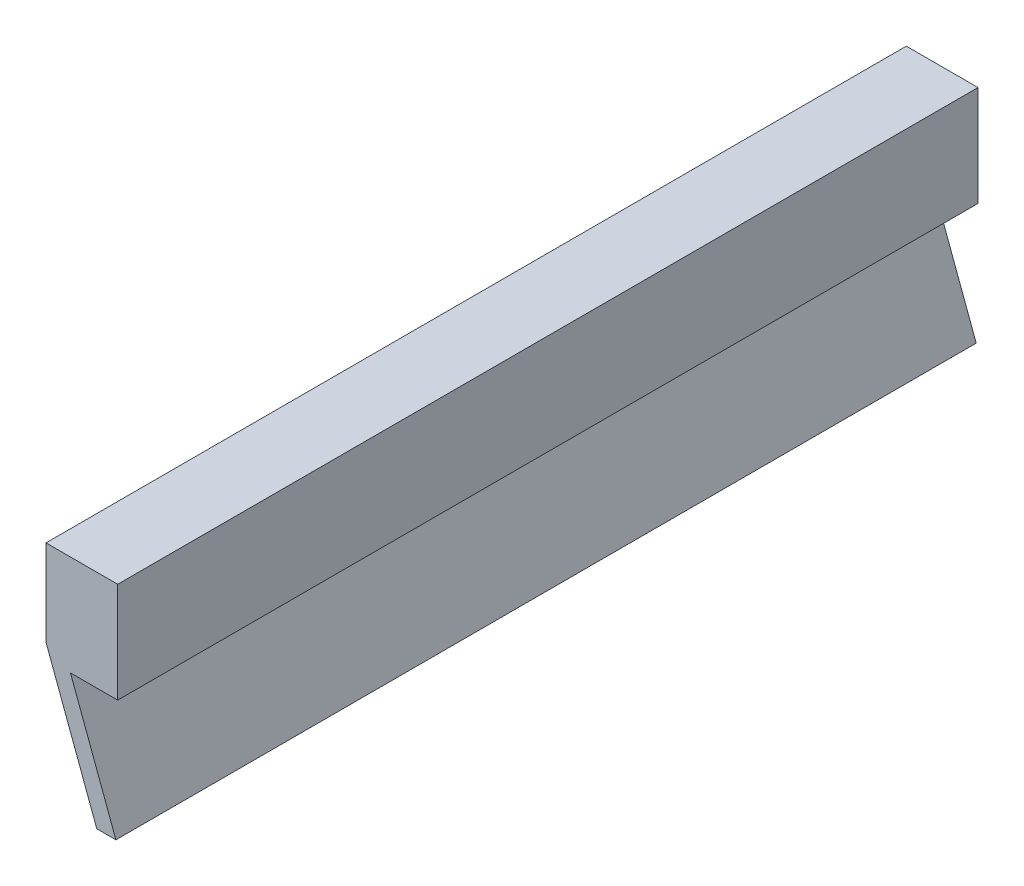
SolidWorks part; units mm, degrees
ref_plane "Alzado" through (0, 0, 0) normal (0, 0, 1) x (1, 0, 0)
ref_plane "Planta" through (0, 0, 0) normal (0, 1, 0) x (1, 0, 0)
ref_plane "Vista lateral" through (0, 0, 0) normal (1, 0, 0) x (0, 0, -1)
sketch "Croquis1" plane through (0, 0, 0) normal (0, 0, 1) x (1, 0, 0)
  line L0 (0, 0) -> (-6.5865, 0)
  line L1 (-6.5865, 0) -> (-0.25, -17)
  line L2 (-0.25, -17) -> (-0.25, -20)
  line L3 (-0.25, -20) -> (-2.918, -20)
  line L4 (-2.918, -20) -> (-2.918, -17)
  line L5 (-2.918, -17) -> (-10, 2)
  line L6 (-10, 2) -> (-10, 14)
  line L7 (-10, 14) -> (0, 14)
  line L8 (0, 14) -> (0, 0)
  line L9 (-0.25, -17) -> (-2.918, -17)
  line L10 (0, 14) -> (0, -24.8871) construction
  dimension "D1" = 2.5
  dimension "D2" = 3
  dimension "D3" = 10
  dimension "D4" = 20
  dimension "D5" = 0.5
  dimension "D6" = 12
  dimension "D7" = 14
extrude "Saliente-Extruir1" add sketch "Croquis1" along normal mid plane 120 contours L9 L1 L0 L8 L7 L6 L5 region at (-4.9199, 3.2174, 0)
